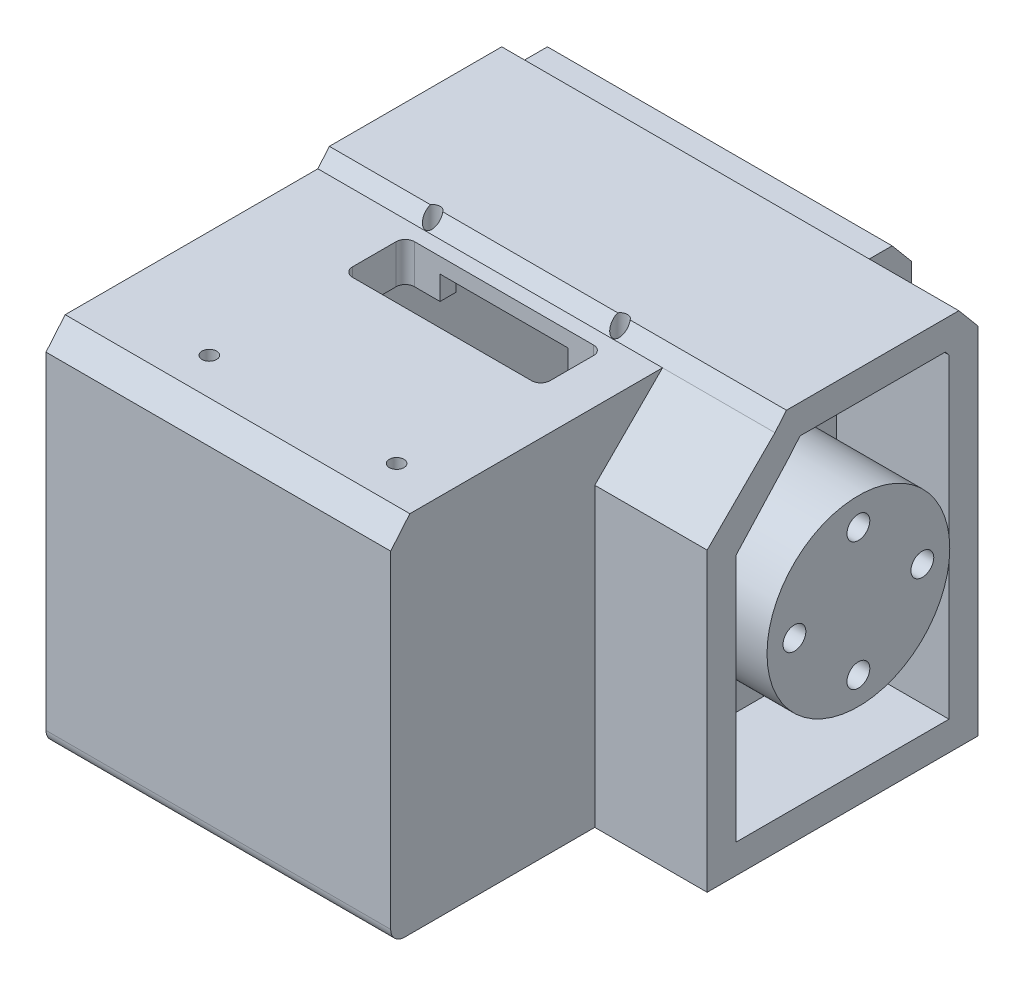
SolidWorks part; units mm, degrees
material "PLA"
ref_plane "Front Plane" through (0, 0, 0) normal (0, 0, 1) x (1, 0, 0)
ref_plane "Top Plane" through (0, 0, 0) normal (0, 1, 0) x (1, 0, 0)
ref_plane "Right Plane" through (0, 0, 0) normal (1, 0, 0) x (0, 0, -1)
sketch "Sketch1" plane through (0, 0, 0) normal (1, 0, 0) x (0, 0, -1)
  line L0 (-25.985, 0) -> (25.985, 0) construction
  line L1 (0, 21.625) -> (0, -21.625) construction
  line L7 (-25.985, -21.625) -> (25.985, -21.625)
  line L8 (-25.985, -21.625) -> (-25.985, 21.625)
  line L9 (-25.985, 21.625) -> (25.985, 21.625)
  line L10 (25.985, -21.625) -> (25.985, 21.625)
  point P5 (0, 0)
  dimension "D1" = 51.97
  dimension "D2" = 43.25
extrude "Boss-Extrude1" add sketch "Sketch1" along normal blind 3.175
sketch "Sketch2" plane through (3.175, 0, 0) normal (1, 0, 0) x (0, 0, -1)
  line L8 (-22.81, 18.45) -> (-22.81, -18.45)
  line L9 (-22.81, -18.45) -> (22.81, -18.45)
  line L10 (22.81, -18.45) -> (22.81, 18.45)
  line L11 (22.81, 18.45) -> (-22.81, 18.45)
  line L12 (-22.81, 18.45) -> (-22.81, -18.45)
  line L13 (-22.81, -18.45) -> (22.81, -18.45)
  line L14 (22.81, -18.45) -> (22.81, 18.45)
  line L15 (22.81, 18.45) -> (-22.81, 18.45)
  line L16 (-25.985, 21.625) -> (-25.985, -21.625)
  line L17 (-25.985, -21.625) -> (25.985, -21.625)
  line L18 (25.985, -21.625) -> (25.985, 21.625)
  line L19 (25.985, 21.625) -> (-25.985, 21.625)
  line L20 (-25.985, 21.625) -> (-25.985, -21.625)
  line L21 (-25.985, -21.625) -> (25.985, -21.625)
  line L22 (25.985, -21.625) -> (25.985, 21.625)
  line L23 (25.985, 21.625) -> (-25.985, 21.625)
  dimension "D1" = 3.175
  dimension "D2" = 0
extrude "Boss-Extrude2" add sketch "Sketch2" along normal blind 25.12
sketch "Sketch5" plane through (0, 18.45, 0) normal (0, -1, 0) x (1, 0, 0)
  line L0 (6.0285, -6.9385) -> (3.175, -6.9385)
  line L1 (25.4415, -6.9385) -> (28.295, -6.9385)
  line L4 (3.175, 22.81) -> (3.175, -22.81)
  line L5 (3.175, -22.81) -> (28.295, -22.81)
  line L6 (28.295, -22.81) -> (28.295, 22.81)
  line L7 (28.295, 22.81) -> (3.175, 22.81)
  line L8 (3.175, 22.81) -> (3.175, -6.9385)
  line L10 (28.295, -6.9385) -> (28.295, 22.81)
  line L11 (28.295, 22.81) -> (3.175, 22.81)
  line L36 (26.535, -2.15) -> (22.735, -2.15)
  line L37 (26.535, 4.625) -> (26.535, -2.15)
  line L38 (25.038, 4.625) -> (26.535, 4.625)
  line L39 (25.1773, 4.8479) -> (25.038, 4.625)
  line L40 (25.1773, 15.8031) -> (25.1773, 4.8479)
  line L41 (7.4927, 17.0031) -> (23.9773, 17.0031)
  line L42 (6.2927, 4.8479) -> (6.2927, 15.8031)
  line L43 (6.432, 4.625) -> (6.2927, 4.8479)
  line L44 (4.935, 4.625) -> (6.432, 4.625)
  line L45 (4.935, -2.15) -> (4.935, 4.625)
  line L46 (8.735, -2.15) -> (4.935, -2.15)
  line L47 (8.735, -3.9136) -> (8.735, -2.15)
  line L48 (4.375, -6.9385) -> (6.0285, -6.9385)
  line L49 (3.875, 20.2102) -> (3.875, -6.4385)
  line L50 (26.0951, 21.71) -> (5.3746, 21.71)
  line L51 (27.595, -6.4385) -> (27.595, 20.2105)
  line L52 (25.4415, -6.9385) -> (27.095, -6.9385)
  line L53 (22.735, -2.15) -> (22.735, -3.9136)
  line L54 (26.535, -2.15) -> (22.735, -2.15)
  line L55 (26.535, 4.625) -> (26.535, -2.15)
  line L56 (25.038, 4.625) -> (26.535, 4.625)
  line L57 (25.1773, 4.8479) -> (25.038, 4.625)
  line L58 (25.1773, 15.8031) -> (25.1773, 4.8479)
  line L59 (7.4927, 17.0031) -> (23.9773, 17.0031)
  line L60 (6.2927, 4.8479) -> (6.2927, 15.8031)
  line L61 (6.432, 4.625) -> (6.2927, 4.8479)
  line L62 (4.935, 4.625) -> (6.432, 4.625)
  line L63 (4.935, -2.15) -> (4.935, 4.625)
  line L64 (8.735, -2.15) -> (4.935, -2.15)
  line L65 (8.735, -3.9136) -> (8.735, -2.15)
  line L71 (22.735, -2.15) -> (22.735, -3.9136)
  arc A12 (25.1773, 15.8031) -> (23.9773, 17.0031) centre (23.9773, 15.8031) ccw
  arc A13 (7.4927, 17.0031) -> (6.2927, 15.8031) centre (7.4927, 15.8031) ccw
  arc A14 (8.735, -3.9136) -> (6.0285, -6.9385) centre (15.735, -12.9) ccw
  arc A15 (3.875, -6.4385) -> (4.375, -6.9385) centre (4.375, -6.4385) ccw
  arc A16 (27.095, -6.9385) -> (27.595, -6.4385) centre (27.095, -6.4385) ccw
  arc A17 (25.4415, -6.9385) -> (22.735, -3.9136) centre (15.735, -12.9) ccw
  arc A18 (25.1773, 15.8031) -> (23.9773, 17.0031) centre (23.9773, 15.8031) ccw
  arc A19 (7.4927, 17.0031) -> (6.2927, 15.8031) centre (7.4927, 15.8031) ccw
  arc A20 (8.735, -3.9136) -> (6.0285, -6.9385) centre (15.735, -12.9) ccw
  arc A23 (25.4415, -6.9385) -> (22.735, -3.9136) centre (15.735, -12.9) ccw
  circle A68 centre (5.485, -4.6) radius 0.8
  circle A69 centre (5.485, 19.85) radius 0.8
  circle A70 centre (25.985, 19.85) radius 0.8
  circle A71 centre (25.985, -4.6) radius 0.8
  spline S4 degree 3 poles (199.8506, -959.1962) (36.727, -55.2614) (14.0519, 23.473) (4.9866, 21.6619) (4.8913, 21.6332) (4.7098, 21.558) (4.6238, 21.5118) (4.4608, 21.403) (4.3836, 21.3399) (4.1763, 21.1325) (4.0645, 20.9654) (1.0086, 13.5957) (53.0588, -19.6485) (521.6785, 875.7094) knots -11.579327 -11.579327 -11.579327 -11.579327 0.125 0.125 0.25 0.25 0.375 0.375 0.5 0.5 0.75 0.75 10.719736 10.719736 10.719736 10.719736 only from (5.3746, 21.71) to (3.875, 20.2102)
  spline S5 degree 3 poles (-953.307, -174.2909) (-49.38, -11.1451) (29.3583, 11.5329) (27.5469, 20.5985) (27.5181, 20.6937) (27.443, 20.8752) (27.3968, 20.9612) (27.288, 21.1242) (27.2248, 21.2014) (27.0175, 21.4088) (26.8503, 21.5206) (19.4805, 24.5762) (-13.7629, -27.4761) (881.6326, -496.0119) knots -11.579675 -11.579675 -11.579675 -11.579675 0.125 0.125 0.25 0.25 0.375 0.375 0.5 0.5 0.75 0.75 10.719832 10.719832 10.719832 10.719832 only from (27.595, 20.2105) to (26.0951, 21.71)
  dimension "D3" = 1.6
  dimension "D1" = 0.2
  dimension "D2" = 0
extrude "Boss-Extrude4" add sketch "Sketch5" along normal blind 2.6
sketch "Sketch6" plane through (0, 18.45, 0) normal (0, -1, 0) x (1, 0, 0)
  line L1 (4.935, 4.625) -> (26.535, 4.625)
  line L2 (4.935, 4.625) -> (4.935, -2.15)
  line L3 (4.935, -2.15) -> (26.535, -2.15)
  line L4 (26.535, 4.625) -> (26.535, -2.15)
  line L18 (6.0285, -6.9385) -> (3.175, -6.9385)
  line L19 (3.175, -6.9385) -> (3.175, -22.81)
  line L20 (3.175, -22.81) -> (28.295, -22.81)
  line L21 (28.295, -22.81) -> (28.295, -6.9385)
  line L22 (28.295, -6.9385) -> (25.4415, -6.9385)
  line L23 (22.735, -3.9136) -> (22.735, -2.15)
  line L24 (22.735, -2.15) -> (26.535, -2.15)
  line L25 (26.535, -2.15) -> (26.535, 4.625)
  line L26 (26.535, 4.625) -> (25.038, 4.625)
  line L27 (25.038, 4.625) -> (25.1773, 4.8479)
  line L28 (25.1773, 4.8479) -> (25.1773, 15.8031)
  line L29 (23.9773, 17.0031) -> (7.4927, 17.0031)
  line L30 (6.2927, 15.8031) -> (6.2927, 4.8479)
  line L31 (6.2927, 4.8479) -> (6.432, 4.625)
  line L32 (6.432, 4.625) -> (4.935, 4.625)
  line L33 (4.935, 4.625) -> (4.935, -2.15)
  line L34 (4.935, -2.15) -> (8.735, -2.15)
  line L35 (8.735, -2.15) -> (8.735, -3.9136)
  line L42 (22.735, -2.15) -> (26.535, -2.15)
  line L43 (26.535, -2.15) -> (26.535, 4.625)
  line L44 (26.535, 4.625) -> (25.038, 4.625)
  line L50 (6.432, 4.625) -> (4.935, 4.625)
  line L51 (4.935, 4.625) -> (4.935, -2.15)
  line L52 (4.935, -2.15) -> (8.735, -2.15)
  arc A4 (8.735, -3.9136) -> (6.0285, -6.9385) centre (15.735, -12.9) ccw
  arc A5 (25.4415, -6.9385) -> (22.735, -3.9136) centre (15.735, -12.9) ccw
  arc A6 (25.1773, 15.8031) -> (23.9773, 17.0031) centre (23.9773, 15.8031) ccw
  arc A7 (7.4927, 17.0031) -> (6.2927, 15.8031) centre (7.4927, 15.8031) ccw
  line M35 (22.735, -2.15) -> (26.535, -2.15)
  line M36 (26.535, -2.15) -> (26.535, 4.625)
  line M37 (26.535, 4.625) -> (25.038, 4.625)
  line M45 (6.432, 4.625) -> (4.935, 4.625)
  line M46 (4.935, 4.625) -> (4.935, -2.15)
  line M47 (4.935, -2.15) -> (8.735, -2.15)
  dimension "D1" = 0
extrude "Cut-Extrude2" cut sketch "Sketch6" against normal through all contours L3 L1 M47 M35 M36 M37 M45 M46
fillet "Fillet4" radius 1 4 edges at (26.535, 18.7375, -2.15) (26.535, 18.7375, 4.625) (4.935, 18.7375, -2.15) (4.935, 18.7375, 4.625)
sketch "Sketch7" plane through (0, 21.625, 0) normal (0, 1, 0) x (1, 0, 0)
  line L0 (28.295, 25.985) -> (28.295, -25.985) construction
  line L1 (0, -25.985) -> (28.295, -25.985)
  line L2 (0, -25.985) -> (0, 3.765)
  line L3 (0, 3.765) -> (28.295, 3.765)
  line L4 (28.295, -25.985) -> (28.295, 3.765)
  line M5 (25.535, -4.625) -> (5.935, -4.625)
  arc M6 (5.935, -4.625) -> (4.935, -3.625) centre (5.935, -3.625) cw
  line M7 (4.935, -3.625) -> (4.935, 1.15)
  arc M8 (4.935, 1.15) -> (5.935, 2.15) centre (5.935, 1.15) cw
  line M9 (5.935, 2.15) -> (25.535, 2.15)
  arc M10 (25.535, 2.15) -> (26.535, 1.15) centre (25.535, 1.15) cw
  line M11 (26.535, 1.15) -> (26.535, -3.625)
  arc M12 (26.535, -3.625) -> (25.535, -4.625) centre (25.535, -3.625) cw
  line M13 (0, 25.985) -> (0, -25.985)
  line M14 (0, -25.985) -> (28.295, -25.985)
  line M15 (28.295, -25.985) -> (28.295, 25.985)
  dimension "D1" = 29.75
extrude "Cut-Extrude3" cut sketch "Sketch7" against normal blind 1.5 contours L3 M13 M14 M15 M12 M5 M6 M7 M8 M9 M10 M11
chamfer "Chamfer3" distance 1.5 angle 40 1 edges at (14.1475, 21.625, -3.765)
chamfer "Chamfer4" distance 2.5 angle 40 1 edges at (14.1475, 20.125, 25.985)
chamfer "Chamfer5" distance 2.5 angle 40 1 edges at (14.1475, 21.625, -25.985)
sketch "Sketch8" plane through (0, -18.45, 0) normal (0, 1, 0) x (1, 0, 0)
  line L1 (8.535, 2.2774) -> (8.535, -21.2062)
  line L6 (22.935, -21.2062) -> (22.935, 2.2774)
  line L8 (5.6661, 6.9407) -> (3.175, 6.9407)
  line L11 (25.803, 6.9392) -> (28.295, 6.9392)
  line L16 (8.8158, -21.9777) -> (8.8158, -22.81)
  line L18 (22.6542, -21.9776) -> (22.6542, -22.81)
  line L19 (3.175, 22.81) -> (3.175, -22.81)
  line L20 (3.175, -22.81) -> (28.295, -22.81)
  line L21 (28.295, -22.81) -> (28.295, 22.81)
  line L22 (28.295, 22.81) -> (3.175, 22.81)
  line L23 (3.175, 6.9407) -> (3.175, -22.81)
  line L24 (3.175, -22.81) -> (8.8158, -22.81)
  line L25 (28.295, -22.81) -> (28.295, 6.9392)
  line L27 (22.6542, -22.81) -> (28.295, -22.81)
  arc A6 (5.6661, 6.9407) -> (9.0755, 3.2799) centre (15.735, 12.9) ccw
  arc A9 (9.0755, 3.2799) -> (8.535, 2.2774) centre (9.735, 2.2774) ccw
  arc A20 (8.535, -21.2062) -> (8.8158, -21.9777) centre (9.735, -21.2062) ccw
  arc A23 (22.6542, -21.9776) -> (22.935, -21.2062) centre (21.735, -21.2062) ccw
  arc A28 (22.935, 2.2774) -> (22.3945, 3.2799) centre (21.735, 2.2774) ccw
  arc A35 (22.3945, 3.2799) -> (25.803, 6.9392) centre (15.735, 12.9) ccw
  circle A56 centre (25.985, -16.1) radius 0.8
  circle A57 centre (5.485, 4.6) radius 0.8
  circle A58 centre (25.985, 4.6) radius 0.8
  circle A59 centre (5.485, -16.1) radius 0.8
  spline S5 degree 3 poles (5.6659, 6.9385) (5.666, 6.9385) (5.6664, 6.9383) (5.6671, 6.938) (5.6678, 6.9375) (5.6681, 6.9373) (5.6683, 6.9372) knots 0.329528 0.329528 0.329528 0.329528 0.414347 0.499166 0.583985 0.668804 0.668804 0.668804 0.668804
  dimension "D1" = 1.6
  dimension "D2" = 1.6
  dimension "D3" = 1.6
  dimension "D4" = 1.6
  dimension "D5" = 0
extrude "Boss-Extrude5" add sketch "Sketch8" along normal blind 1.9
sketch "Sketch9" plane through (0, 18.45, 0) normal (0, -1, 0) x (1, 0, 0)
  circle A0 centre (5.485, -4.6) radius 0.8 construction
  circle A1 centre (25.985, -4.6) radius 0.8 construction
  circle A2 centre (25.985, 19.85) radius 0.8 construction
  circle A3 centre (5.485, 19.85) radius 0.8 construction
  circle A4 centre (5.485, -4.6) radius 0.8
  circle A5 centre (25.985, -4.6) radius 0.8
  circle A6 centre (25.985, 19.85) radius 0.8
  circle A7 centre (5.485, 19.85) radius 0.8
extrude "Cut-Extrude4" cut sketch "Sketch9" against normal through all
sketch "Sketch10" plane through (0, -21.625, 0) normal (0, -1, 0) x (1, 0, 0)
  line L0 (28.295, 25.985) -> (28.295, -25.985) construction
  line L1 (0, 25.985) -> (28.295, 25.985)
  line L2 (0, 25.985) -> (0, -6.935)
  line L3 (0, -6.935) -> (28.295, -6.935)
  line L4 (28.295, 25.985) -> (28.295, -6.935)
  dimension "D1" = 32.92
extrude "Cut-Extrude5" cut sketch "Sketch10" against normal blind 1.9
chamfer "Chamfer6" distance 1.9 angle 40 1 edges at (14.1475, -19.725, -6.935)
sketch "Sketch11" plane through (0, -18.45, 0) normal (0, 1, 0) x (1, 0, 0)
  line L10 (3.175, 22.81) -> (3.175, 6.9407)
  line L11 (3.175, 6.9407) -> (5.6661, 6.9407)
  line L12 (8.535, 2.2774) -> (8.535, -21.2062)
  line L13 (8.8158, -21.9777) -> (8.8158, -22.81)
  line L14 (8.8158, -22.81) -> (22.6542, -22.81)
  line L15 (22.6542, -22.81) -> (22.6542, -21.9776)
  line L16 (22.935, -21.2062) -> (22.935, 2.2774)
  line L17 (25.803, 6.9392) -> (28.295, 6.9392)
  line L18 (28.295, 6.9392) -> (28.295, 22.81)
  line L19 (28.295, 22.81) -> (3.175, 22.81)
  line L20 (3.175, 22.81) -> (3.175, 6.9407)
  line L21 (3.175, 6.9407) -> (5.6661, 6.9407)
  line L27 (25.803, 6.9392) -> (28.295, 6.9392)
  line L28 (28.295, 6.9392) -> (28.295, 22.81)
  line L29 (28.295, 22.81) -> (3.175, 22.81)
  arc A0 (9.0755, 3.2799) -> (22.3945, 3.2799) centre (15.735, 9.9394) ccw
  arc A6 (5.6661, 6.9407) -> (9.0755, 3.2799) centre (15.735, 12.9) ccw
  arc A7 (9.0755, 3.2799) -> (8.535, 2.2774) centre (9.735, 2.2774) ccw
  arc A8 (8.535, -21.2062) -> (8.8158, -21.9777) centre (9.735, -21.2062) ccw
  arc A9 (22.6542, -21.9776) -> (22.935, -21.2062) centre (21.735, -21.2062) ccw
  arc A10 (22.935, 2.2774) -> (22.3945, 3.2799) centre (21.735, 2.2774) ccw
  arc A11 (22.3945, 3.2799) -> (25.803, 6.9392) centre (15.735, 12.9) ccw
  arc A12 (5.6661, 6.9407) -> (9.0755, 3.2799) centre (15.735, 12.9) ccw
  arc A17 (22.3945, 3.2799) -> (25.803, 6.9392) centre (15.735, 12.9) ccw
  dimension "D1" = 0
extrude "Cut-Extrude6" cut sketch "Sketch11" against normal through all
sketch "Sketch12" plane through (0, -18.45, 0) normal (0, 1, 0) x (1, 0, 0)
  circle A0 centre (25.985, 4.6) radius 0.8 construction
  circle A1 centre (25.985, -16.1) radius 0.8 construction
  circle A2 centre (5.485, -16.1) radius 0.8 construction
  circle A3 centre (5.485, 4.6) radius 0.8 construction
  circle A4 centre (25.985, 4.6) radius 0.8
  circle A5 centre (25.985, -16.1) radius 0.8
  circle A6 centre (5.485, -16.1) radius 0.8
  circle A7 centre (5.485, 4.6) radius 0.8
extrude "Cut-Extrude7" cut sketch "Sketch12" against normal through all
sketch "Sketch13" plane through (0, -21.625, 0) normal (0, -1, 0) x (1, 0, 0)
  line L0 (28.295, -5.3407) -> (28.295, 25.985) construction
  line L1 (0, -25.985) -> (28.295, -25.985)
  line L2 (0, -25.985) -> (0, 7.0246)
  line L3 (0, 7.0246) -> (28.295, 7.0246)
  line L4 (28.295, -25.985) -> (28.295, 7.0246)
extrude "Cut-Extrude8" cut sketch "Sketch13" against normal up to surface (1.9 mm away) up to face at (15.2058, -19.725, 0.7228)
sketch "Sketch14" plane through (28.295, 0, 0) normal (1, 0, 0) x (0, 0, -1)
  line L0 (6.9392, -16.55) -> (22.81, -16.55)
  line L1 (6.9392, -19.725) -> (22.81, -19.725)
  line L3 (6.9392, -16.55) -> (22.81, -16.55)
  line L5 (6.9392, -19.725) -> (22.81, -19.725)
  line L16 (-25.985, -19.725) -> (6.9392, -19.725)
  line L17 (6.9392, -19.725) -> (6.9392, -16.55)
  line L18 (6.9392, -16.55) -> (-22.81, -16.55)
  line L19 (-22.81, -16.55) -> (-22.81, 15.85)
  line L20 (-22.81, 15.85) -> (6.9385, 15.85)
  line L21 (6.9385, 15.85) -> (6.9385, 18.45)
  line L22 (6.9385, 18.45) -> (22.81, 18.45)
  line L23 (22.81, 18.45) -> (22.81, -19.725)
  line L24 (22.81, -19.725) -> (25.985, -19.725)
  line L25 (25.985, -19.725) -> (25.985, 19.125)
  line L26 (25.985, 19.125) -> (23.8873, 21.625)
  line L27 (23.8873, 21.625) -> (5.0236, 21.625)
  line L28 (5.0236, 21.625) -> (3.765, 20.125)
  line L29 (3.765, 20.125) -> (-23.8873, 20.125)
  line L30 (-23.8873, 20.125) -> (-25.985, 17.625)
  line L31 (-25.985, 17.625) -> (-25.985, -19.725)
  line L32 (-25.985, -19.725) -> (6.9392, -19.725)
  line L34 (6.9392, -16.55) -> (-22.81, -16.55)
  line L35 (-22.81, -16.55) -> (-22.81, 15.85)
  line L36 (-22.81, 15.85) -> (6.9385, 15.85)
  line L37 (6.9385, 15.85) -> (6.9385, 18.45)
  line L38 (6.9385, 18.45) -> (22.81, 18.45)
  line L39 (22.81, 18.45) -> (22.81, -16.55)
  line L40 (22.81, -19.725) -> (25.985, -19.725)
  line L41 (25.985, -19.725) -> (25.985, 19.125)
  line L42 (25.985, 19.125) -> (23.8873, 21.625)
  line L43 (23.8873, 21.625) -> (5.0236, 21.625)
  line L44 (5.0236, 21.625) -> (3.765, 20.125)
  line L45 (3.765, 20.125) -> (-23.8873, 20.125)
  line L46 (-23.8873, 20.125) -> (-25.985, 17.625)
  line L47 (-25.985, 17.625) -> (-25.985, -19.725)
  line M21 (-25.985, -19.725) -> (6.9392, -19.725)
  line M22 (6.9392, -19.725) -> (6.9392, -16.55)
  line M23 (6.9392, -16.55) -> (-22.81, -16.55)
  line M24 (-22.81, -16.55) -> (-22.81, 15.85)
  line M25 (-22.81, 15.85) -> (6.9385, 15.85)
  line M26 (6.9385, 15.85) -> (6.9385, 18.45)
  line M27 (6.9385, 18.45) -> (22.81, 18.45)
  line M28 (22.81, 18.45) -> (22.81, -19.725)
  line M29 (22.81, -19.725) -> (25.985, -19.725)
  line M30 (25.985, -19.725) -> (25.985, 19.125)
  line M31 (25.985, 19.125) -> (23.8873, 21.625)
  line M32 (23.8873, 21.625) -> (5.0236, 21.625)
  line M33 (5.0236, 21.625) -> (3.765, 20.125)
  line M34 (3.765, 20.125) -> (-23.8873, 20.125)
  line M35 (-23.8873, 20.125) -> (-25.985, 17.625)
  line M36 (-25.985, 17.625) -> (-25.985, -19.725)
  dimension "D1" = 0
extrude "Boss-Extrude6" add sketch "Sketch14" along normal blind 3.175 contours M36 M21 M22 M23 M24 M25 M26 M27 M28 M29 M30 M31 M32 M33 M34 M35 | L1 L0 M22 M28
sketch "Sketch15" plane through (31.47, 0, 0) normal (1, 0, 0) x (0, 0, -1)
  line L0 (25.985, 0) -> (12.495, 0) construction
  line L1 (25.985, -19.725) -> (25.985, 19.125) construction
  circle A0 centre (12.495, 0) radius 10
  circle A1 centre (12.495, 0) radius 7 construction
  circle A2 centre (12.495, 7) radius 1.25
  circle A3 centre (19.495, 0) radius 1.25
  circle A4 centre (5.495, 0) radius 1.25
  circle A5 centre (12.495, -7) radius 1.25
  dimension "D2" = 20
  dimension "D3" = 14
  dimension "D4" = 2.5
  dimension "D1" = 13.49
extrude "Boss-Extrude7" add sketch "Sketch15" along normal blind 12.7
sketch "Sketch16" plane through (31.47, 0, 0) normal (1, 0, 0) x (0, 0, -1)
  circle A0 centre (19.495, 0) radius 1.25 construction
  circle A1 centre (12.495, -7) radius 1.25 construction
  circle A2 centre (5.495, 0) radius 1.25 construction
  circle A3 centre (12.495, 7) radius 1.25 construction
  circle A4 centre (19.495, 0) radius 1.25
  circle A5 centre (12.495, -7) radius 1.25
  circle A6 centre (5.495, 0) radius 1.25
  circle A7 centre (12.495, 7) radius 1.25
extrude "Cut-Extrude9" cut sketch "Sketch16" against normal up to surface (3.175 mm away) up to face at (28.295, -0.4938, -3.4694)
sketch "Sketch17" plane through (31.47, 0, 0) normal (1, 0, 0) x (0, 0, -1)
  line L1 (-0.4777, -16.55) -> (22.81, -16.55)
  line L2 (22.81, -16.55) -> (22.81, 17.9694)
  line L3 (22.81, 17.9694) -> (22.4067, 18.45)
  line L4 (22.4067, 18.45) -> (6.5042, 18.45)
  line L5 (6.5042, 18.45) -> (5.2455, 16.95)
  line L8 (-25.985, 17.625) -> (-25.985, -19.725)
  line L9 (-25.985, -19.725) -> (25.985, -19.725)
  line L10 (25.985, -19.725) -> (25.985, 19.125)
  line L11 (25.985, 19.125) -> (23.8873, 21.625)
  line L12 (23.8873, 21.625) -> (5.0236, 21.625)
  line L13 (5.0236, 21.625) -> (3.765, 20.125)
  line L14 (3.765, 20.125) -> (-23.8873, 20.125)
  line L15 (-23.8873, 20.125) -> (-25.985, 17.625)
  line L18 (25.985, -19.725) -> (25.985, 19.125)
  line L19 (25.985, 19.125) -> (23.8873, 21.625)
  line L20 (23.8873, 21.625) -> (5.0236, 21.625)
  line L21 (5.0236, 21.625) -> (3.765, 20.125)
  line L24 (5.2455, 16.95) -> (-0.4777, 10.6655)
  line L25 (-0.4777, 10.6655) -> (-0.4777, -16.55)
  line L26 (-3.6527, -16.55) -> (-3.6527, -19.725)
  line L27 (-3.6527, 11.6724) -> (-3.6527, -16.55)
  line L28 (3.765, 20.125) -> (-3.6527, 12.7073)
  line L29 (5.2455, 16.95) -> (-22.4067, 16.95) construction
  line L30 (-3.6527, 12.7073) -> (-3.6527, 11.6724)
  line L31 (-22.81, -16.55) -> (22.81, -16.55) construction
  line L32 (3.765, 20.125) -> (-23.8873, 20.125) construction
  line L33 (-23.8873, 20.125) -> (-25.985, 17.625) construction
  line L34 (-25.985, 17.625) -> (-25.985, -19.725) construction
  line L35 (-22.81, 16.4694) -> (-22.81, -16.55) construction
  line L36 (-22.4067, 16.95) -> (-22.81, 16.4694) construction
  line L37 (-25.985, -19.725) -> (25.985, -19.725) construction
  line L38 (-25.985, -19.725) -> (25.985, -19.725) construction
  line L39 (-3.6527, -19.725) -> (25.985, -19.725)
  dimension "D3" = 8.5
  dimension "D4" = 3.175
  dimension "D1" = 0
  dimension "D2" = 3.175
extrude "Boss-Extrude8" add sketch "Sketch17" along normal blind 12.3
sketch "Sketch18" plane through (0, 0, 0) normal (-1, 0, 0) x (0, 0, 1)
  line L8 (-25.985, 19.125) -> (-25.985, -19.725)
  line L9 (-25.985, -19.725) -> (25.985, -19.725)
  line L10 (25.985, -19.725) -> (25.985, 17.625)
  line L11 (25.985, 17.625) -> (23.8873, 20.125)
  line L12 (23.8873, 20.125) -> (-3.765, 20.125)
  line L13 (-3.765, 20.125) -> (-5.0236, 21.625)
  line L14 (-5.0236, 21.625) -> (-23.8873, 21.625)
  line L15 (-23.8873, 21.625) -> (-25.985, 19.125)
  line L16 (-25.985, 19.125) -> (-25.985, -19.725)
  line L17 (-25.985, -19.725) -> (25.985, -19.725)
  line L18 (25.985, -19.725) -> (25.985, 17.625)
  line L19 (25.985, 17.625) -> (23.8873, 20.125)
  line L20 (23.8873, 20.125) -> (-3.765, 20.125)
  line L21 (-3.765, 20.125) -> (-5.0236, 21.625)
  line L22 (-5.0236, 21.625) -> (-23.8873, 21.625)
  line L23 (-23.8873, 21.625) -> (-25.985, 19.125)
  dimension "D1" = 0
extrude "Boss-Extrude9" add sketch "Sketch18" along normal blind 6.25
sketch "Sketch19" plane through (-6.25, 0, 0) normal (-1, 0, 0) x (0, 0, 1)
  line L0 (-25.985, 19.125) -> (-30.985, 19.125)
  line L1 (-30.985, 19.125) -> (-30.985, -19.725)
  line L2 (-30.985, -19.725) -> (-25.985, -19.725)
  line L3 (-25.985, -19.725) -> (-25.985, 19.125)
  dimension "D1" = 5
extrude "Boss-Extrude10" add sketch "Sketch19" against normal up to surface (37.72 mm away) up to face at (31.47, 7.055, -11.2601)
chamfer "Chamfer7" distance 2.5 angle 40 1 edges at (12.61, 19.125, -30.985)
fillet "Fillet5" radius 1.5 2 edges at (12.61, -19.725, 25.985) (12.61, -19.725, -30.985)
sketch "Sketch20" plane through (-6.25, 0, 0) normal (-1, 0, 0) x (0, 0, 1)
  line L38 (-25.985, 14.125) -> (-25.985, -14.725)
  line L39 (-25.985, -14.725) -> (20.985, -14.725)
  line L40 (20.985, -14.725) -> (20.985, 15.125)
  line L41 (20.985, 15.125) -> (-6.0965, 15.125)
  line L42 (-6.0965, 15.125) -> (-7.3552, 16.625)
  line L43 (-7.3552, 16.625) -> (-21.5557, 16.625)
  line L44 (-21.5557, 16.625) -> (-23.6535, 14.125)
  line L45 (-23.6535, 14.125) -> (-25.985, 14.125)
  line L46 (-25.985, 14.125) -> (-25.985, -12.225)
  line L47 (-23.485, -14.725) -> (18.485, -14.725)
  line L48 (20.985, -12.225) -> (20.985, 12.625)
  line L49 (18.485, 15.125) -> (-6.0965, 15.125)
  line L50 (-6.0965, 15.125) -> (-7.3552, 16.625)
  line L51 (-7.3552, 16.625) -> (-21.5557, 16.625)
  line L52 (-21.5557, 16.625) -> (-23.6535, 14.125)
  line L53 (-23.6535, 14.125) -> (-25.985, 14.125)
  arc A8 (-25.985, -12.225) -> (-23.485, -14.725) centre (-23.485, -12.225) ccw
  arc A9 (18.485, -14.725) -> (20.985, -12.225) centre (18.485, -12.225) ccw
  arc A10 (20.985, 12.625) -> (18.485, 15.125) centre (18.485, 12.625) ccw
  dimension "D2" = 2.5
  dimension "D1" = 5
extrude "Boss-Extrude11" add sketch "Sketch20" along normal blind 1
chamfer "Chamfer8" distance 1 angle 40 11 edges at (-7.25, 0.95, -25.985) (-7.25, 14.125, -24.8192) (-7.25, 15.375, -22.6046) (-7.25, 16.625, -14.4555) (-7.25, 15.875, -6.7259) (-7.25, 15.125, 6.1942) (-7.25, 14.3928, 20.2528) (-7.25, 0.2, 20.985) (-7.25, -13.9928, 20.2528) (-7.25, -14.725, -2.5) (-7.25, -13.9928, -25.2528)
sketch "Sketch21" plane through (0, -16.55, 0) normal (0, 1, 0) x (1, 0, 0)
  line L0 (3.175, -7.9346) -> (28.295, -7.9354)
  line L5 (5.6661, 6.9407) -> (3.175, 6.9407)
  line L6 (3.175, 6.9407) -> (3.175, -22.81)
  line L7 (3.175, -22.81) -> (8.8158, -22.81)
  line L8 (8.8158, -22.81) -> (8.8158, -21.9777)
  line L9 (8.535, -21.2062) -> (8.535, 2.2774)
  line L10 (5.6661, 6.9407) -> (3.175, 6.9407)
  line L11 (3.175, 6.9407) -> (3.175, -7.9346)
  line L15 (22.935, 2.2774) -> (22.935, -21.2062)
  line L16 (22.6542, -21.9776) -> (22.6542, -22.81)
  line L17 (22.6542, -22.81) -> (28.295, -22.81)
  line L18 (28.295, -22.81) -> (28.295, 6.9392)
  line L19 (28.295, 6.9392) -> (25.803, 6.9392)
  line L23 (28.295, -7.9354) -> (28.295, 6.9392)
  line L24 (28.295, 6.9392) -> (25.803, 6.9392)
  line L25 (8.535, 2.2774) -> (8.535, -21.2062)
  line L26 (8.8158, -21.9777) -> (8.8158, -22.81)
  line L27 (8.8158, -22.81) -> (22.6542, -22.81)
  line L28 (22.6542, -22.81) -> (22.6542, -21.9776)
  line L29 (22.935, -21.2062) -> (22.935, 2.2774)
  arc A3 (5.6661, 6.9407) -> (9.0755, 3.2799) centre (15.735, 12.9) ccw
  arc A4 (8.535, -21.2062) -> (8.8158, -21.9777) centre (9.735, -21.2062) ccw
  arc A5 (9.0755, 3.2799) -> (8.535, 2.2774) centre (9.735, 2.2774) ccw
  arc A6 (5.6661, 6.9407) -> (9.0755, 3.2799) centre (15.735, 12.9) ccw
  arc A9 (22.3945, 3.2799) -> (25.803, 6.9392) centre (15.735, 12.9) ccw
  arc A10 (22.935, 2.2774) -> (22.3945, 3.2799) centre (21.735, 2.2774) ccw
  arc A11 (22.6542, -21.9776) -> (22.935, -21.2062) centre (21.735, -21.2062) ccw
  arc A12 (22.3945, 3.2799) -> (25.803, 6.9392) centre (15.735, 12.9) ccw
  arc A17 (9.0755, 3.2799) -> (22.3945, 3.2799) centre (15.735, 9.9394) ccw
  arc A18 (9.0755, 3.2799) -> (8.535, 2.2774) centre (9.735, 2.2774) ccw
  arc A19 (8.535, -21.2062) -> (8.8158, -21.9777) centre (9.735, -21.2062) ccw
  arc A20 (22.6542, -21.9776) -> (22.935, -21.2062) centre (21.735, -21.2062) ccw
  arc A21 (22.935, 2.2774) -> (22.3945, 3.2799) centre (21.735, 2.2774) ccw
  arc A22 (9.0755, 3.2799) -> (22.3945, 3.2799) centre (15.735, 9.9394) ccw
  dimension "D1" = 0
  dimension "D2" = 0
  dimension "D3" = 0
extrude "Cut-Extrude10" cut sketch "Sketch21" against normal through all
chamfer "Chamfer9" distance 6.35 angle 45 1 edges at (15.735, -19.725, -22.81)
